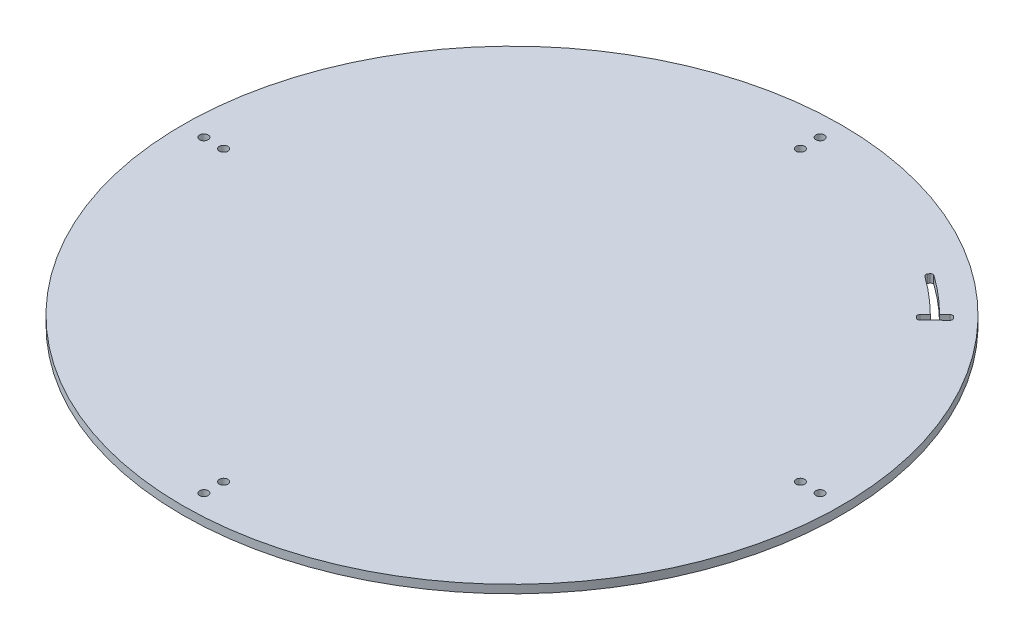
SolidWorks part; units mm, degrees
ref_plane "前视基准面" through (0, 0, 0) normal (0, 0, 1) x (1, 0, 0)
ref_plane "上视基准面" through (0, 0, 0) normal (0, 1, 0) x (1, 0, 0)
ref_plane "右视基准面" through (0, 0, 0) normal (1, 0, 0) x (0, 0, -1)
ref_axis "中心轴" through (0, -55, 0) along (0, 1, 0)
sketch "草图1" plane through (0, 0, 0) normal (0, 1, 0) x (1, 0, 0)
  circle A0 centre (0, 0) radius 200
extrude "主体" add sketch "草图1" along normal blind 5
sketch "草图2" plane through (0, 5, 0) normal (0, 1, 0) x (1, 0, 0)
  line L0 (0, 0) -> (0, 120.98) construction
  circle A0 centre (0, 0) radius 200
  circle A1 centre (0, 0) radius 187 construction
  circle A2 centre (0, 0) radius 200 construction
  circle A3 centre (0, 0) radius 175 construction
  circle A6 centre (0, -175) radius 2.6
  circle A7 centre (0, -187) radius 2.6
extrude "切除-拉伸3" cut sketch "草图2" against normal up to next contours A6 | A7 region at (0, 5, 175) region at (0, 5, 187)
pattern_circular "阵列(圆周)1" count 4 over 360 about axis through (0, -55, 0) along (0, 1, 0) of "切除-拉伸3"
sketch "草图4" plane through (0, 0, 0) normal (0.7105, 0, 0.7037) x (0.7037, 0, -0.7105)
  line L1 (180, 10.5) -> (183, 10.5) construction
  line L2 (180, 10.5) -> (180, 0) construction
  line L3 (180, 0) -> (183, 0) construction
  line L4 (183, 10.5) -> (183, 0) construction
  line L5 (183.5, 11) -> (183.5, -0.5)
  line L6 (179.5, -0.5) -> (183.5, -0.5)
  line L7 (179.5, 11) -> (179.5, -0.5)
  line L8 (179.5, 11) -> (183.5, 11)
  dimension "D1" = 0.5
revolve "切除-旋转3" cut sketch "草图4" angle 9.5 about axis through (0, -55, 0) along (0, 1, 0) other way angle 0.5
fillet "圆角2" radius 1.5 2 edges at (103.5255, 2.5, -146.638) (105.8325, 2.5, -149.9057)
sketch "草图6" plane through (0, 5, 0) normal (0, 1, 0) x (1, 0, 0)
  line L0 (123.0366, 123.0366) -> (133.6432, 133.6432) construction
  line L1 (126.2395, 121.9081) -> (134.8719, 130.2443) construction
  line L4 (135.9552, 131.2904) -> (125.1651, 120.8706) construction
  line L6 (124.0927, 124.0927) -> (132.5783, 132.5783) construction
  line L8 (122.329, 123.0361) -> (133.6427, 134.3498)
  line L9 (136.6617, 131.2776) -> (125.1523, 120.1631)
  line L10 (139.3566, 127.8395) -> (130.2521, 137.1042) construction
  line L11 (121.0961, 125.0207) -> (127.1151, 118.8957) construction
  arc A0 (135.9552, 131.2904) -> (133.6432, 133.6432) centre (0, 0) ccw construction
  arc A1 (125.1651, 120.8706) -> (123.0366, 123.0366) centre (0, 0) ccw construction
  arc A4 (136.6617, 131.2776) -> (133.6427, 134.3498) centre (0, 0) ccw
  arc A5 (125.1523, 120.1631) -> (122.329, 123.0361) centre (0, 0) ccw
  dimension "D1" = 0.5
extrude "开孔" cut sketch "草图6" against normal up to next
fillet "圆角1" radius 1.5 4 edges at (125.1523, 2.5, -120.1631) (136.6617, 2.5, -131.2776) (133.6427, 2.5, -134.3498) (122.329, 2.5, -123.0361)
